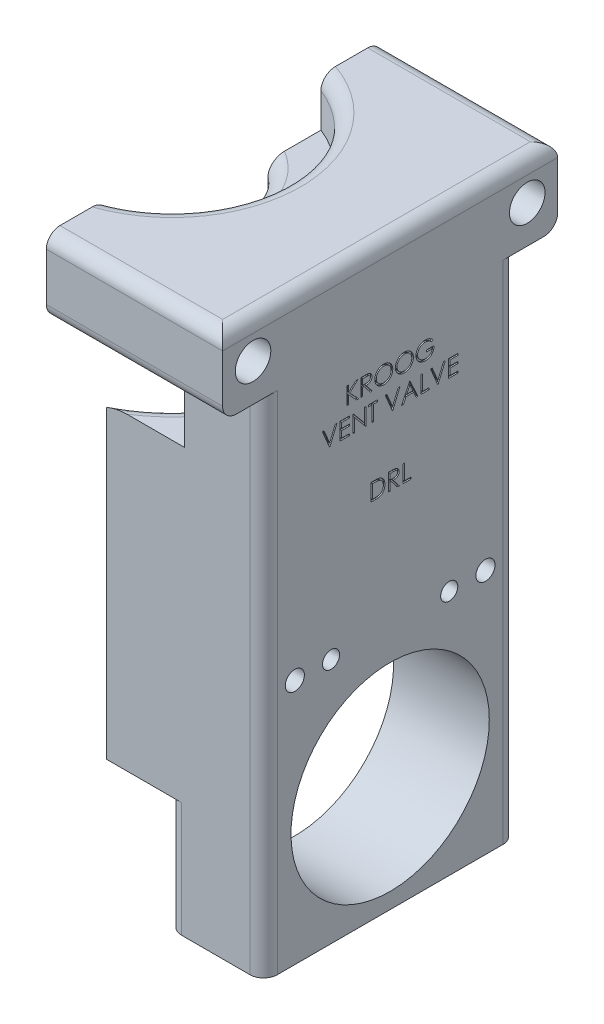
SolidWorks part; units mm, degrees
material "ABS"
ref_plane "Front Plane" through (0, 0, 0) normal (0, 0, 1) x (1, 0, 0)
ref_plane "Top Plane" through (0, 0, 0) normal (0, 1, 0) x (1, 0, 0)
ref_plane "Right Plane" through (0, 0, 0) normal (1, 0, 0) x (0, 0, -1)
sketch "Sketch2" plane through (0, 0, 0) normal (1, 0, 0) x (0, 0, -1)
  line L7 (-23.495, -21.336) -> (23.495, -21.336)
  line L8 (-23.495, -21.336) -> (-23.495, 72.644)
  line L9 (-23.495, 86.614) -> (23.495, 86.614)
  line L10 (23.495, -21.336) -> (23.495, 72.644)
  line L11 (-23.495, 86.614) -> (-31.115, 86.614)
  line L13 (-23.495, 72.644) -> (-31.115, 72.644)
  line L14 (-31.115, 86.614) -> (-31.115, 72.644)
  line L15 (23.495, 86.614) -> (31.115, 86.614)
  line L17 (23.495, 72.644) -> (31.115, 72.644)
  line L18 (31.115, 86.614) -> (31.115, 72.644)
  circle A0 centre (0, 0) radius 18.415
  point P13 (0, -21.336)
  dimension "D1" = 36.83
  dimension "D2" = 21.336
  dimension "D3" = 46.99
  dimension "D4" = 107.95
  dimension "D5" = 13.97
  dimension "D6" = 7.62
extrude "Boss-Extrude1" add sketch "Sketch2" along normal blind 17.78
sketch "Sketch4" plane through (0, 0, 0) normal (-1, 0, 0) x (0, 0, 1)
  line L0 (-23.495, -21.336) -> (-23.495, 72.644) construction
  line L1 (-23.495, 18.796) -> (23.495, 18.796)
  line L2 (-23.495, 18.796) -> (-23.495, 72.644)
  line L4 (23.495, 18.796) -> (23.495, 72.644)
  line L5 (31.115, 86.614) -> (31.115, 72.644) construction
  line L6 (31.115, 72.644) -> (23.495, 72.644) construction
  line L7 (-23.495, 72.644) -> (-31.115, 72.644) construction
  line L8 (-31.115, 72.644) -> (-31.115, 86.614) construction
  line L9 (-31.115, 86.614) -> (31.115, 86.614) construction
  line L10 (31.115, 86.614) -> (31.115, 72.644)
  line L11 (31.115, 72.644) -> (23.495, 72.644)
  line L12 (-23.495, 72.644) -> (-31.115, 72.644)
  line L13 (-31.115, 72.644) -> (-31.115, 86.614)
  line L14 (-31.115, 86.614) -> (31.115, 86.614)
  line L15 (23.495, 72.644) -> (23.495, -21.336) construction
  dimension "D1" = 18.796
extrude "Boss-Extrude2" add sketch "Sketch4" along normal blind 11.43
sketch "Sketch5" plane through (0, 86.614, 0) normal (0, 1, 0) x (1, 0, 0)
  line L0 (0, 0) -> (-22.7305, 0) construction
  line L2 (-11.43, -31.115) -> (-11.43, 31.115) construction
  circle A0 centre (-22.7305, 0) radius 34.925
  circle A1 centre (-22.7305, 0) radius 25.4
  dimension "D2" = 69.85
  dimension "D3" = 50.8
  dimension "D1" = 11.3005
extrude "Cut-Extrude1" cut sketch "Sketch5" against normal blind 15.24 from offset 13.97 contours A1 A0 | A1 region at (-56.6676, 86.614, 0) region at (-22.7305, 86.614, 0) offset against normal yes
extrude "Cut-Extrude2" cut sketch "Sketch5<3>" against normal blind 41.91 from surface contours A1 region at (-22.7305, 86.614, 0) starting at face at (-1.8888, 57.404, 0)
sketch "Sketch5<3>" plane through (0, 86.614, 0) normal (0, 1, 0) x (1, 0, 0) same geometry as "Sketch5"
sketch "Sketch6" plane through (-11.43, 0, 0) normal (-1, 0, 0) x (0, 0, 1)
  line L4 (-31.115, 86.614) -> (-31.115, 72.644)
  line L5 (-31.115, 72.644) -> (31.115, 72.644)
  line L6 (-31.115, 86.614) -> (-31.115, 72.644)
  line L7 (31.115, 72.644) -> (31.115, 86.614)
  line L9 (-31.115, 72.644) -> (31.115, 72.644)
  line L12 (31.115, 72.644) -> (31.115, 86.614)
  line L13 (31.115, 86.614) -> (-31.115, 86.614)
  line L14 (31.115, 86.614) -> (-31.115, 86.614)
  dimension "D1" = 0
extrude "Boss-Extrude3" add sketch "Sketch6" along normal blind 3.5301
sketch "Sketch12" plane through (0, 0, 0) normal (-1, 0, 0) x (0, 0, 1)
  line L0 (-23.495, 18.796) -> (-11.3352, 18.796) construction
  line L1 (-23.495, 18.796) -> (-11.3352, 18.796)
  line L2 (-19.05, 0) -> (-23.495, 0)
  line L3 (-23.495, -21.336) -> (-23.495, 18.796) construction
  line L4 (-23.495, 0) -> (-23.495, 18.796)
  line L5 (19.05, 0) -> (23.495, 0)
  line L6 (11.3352, 18.796) -> (23.495, 18.796)
  line L7 (23.495, 0) -> (23.495, 18.796)
  line L8 (23.495, 18.796) -> (23.495, -21.336) construction
  line L9 (-11.3352, 18.796) -> (-11.3352, 15.3107)
  line L10 (-11.3352, 15.494) -> (-11.3352, 18.796) construction
  line L11 (11.3352, 18.796) -> (11.3352, 15.3107)
  line L12 (11.3352, 18.796) -> (11.3352, 15.494) construction
  arc A0 (-19.05, 0) -> (-11.3352, 15.3107) centre (0, 0) cw
  arc A1 (11.3352, 15.3107) -> (19.05, 0) centre (0, 0) cw
  dimension "D1" = 19.05
extrude "Boss-Extrude5" add sketch "Sketch12" along normal up to surface (11.43 mm away) up to face at (-11.43, 38.1, 23.1214)
sketch "Sketch13" plane through (17.78, 0, 0) normal (1, 0, 0) x (0, 0, -1)
  line L0 (-23.495, -21.336) -> (23.495, -21.336) construction
  line L1 (-23.495, 72.644) -> (-23.495, -21.336) construction
  line L2 (0, 0) -> (0, 86.614) construction
  line L4 (31.115, 86.614) -> (-31.115, 86.614) construction
  circle A0 centre (-17.7038, 24.384) radius 1.778
  circle A1 centre (-10.9728, 24.384) radius 1.5875
  circle A2 centre (17.7038, 24.384) radius 1.778
  circle A3 centre (10.9728, 24.384) radius 1.5875
  dimension "D3" = 3.556
  dimension "D5" = 3.175
  dimension "D1" = 45.72
  dimension "D2" = 5.7912
  dimension "D4" = 6.731
extrude "Cut-Extrude5" cut sketch "Sketch13" against normal through all
sketch "Sketch14" plane through (-11.43, 0, 0) normal (-1, 0, 0) x (0, 0, 1)
  line L0 (10.9728, 24.384) -> (17.7038, 24.384) construction
  line L1 (10.9728, 27.432) -> (17.7038, 27.432)
  line L2 (10.9728, 21.336) -> (17.7038, 21.336)
  line L3 (0, 0) -> (0, 57.404) construction
  line L5 (22.7477, 57.404) -> (-22.7477, 57.404) construction
  line L6 (-10.9728, 24.384) -> (-17.7038, 24.384) construction
  line L7 (-10.9728, 27.432) -> (-17.7038, 27.432)
  line L8 (-10.9728, 21.336) -> (-17.7038, 21.336)
  line L9 (-7.9248, 24.384) -> (-7.9248, 21.336)
  line L10 (-20.7518, 49.784) -> (-7.9248, 49.784)
  line L11 (-20.7518, 49.784) -> (-20.7518, 24.384)
  line L12 (-20.7518, 24.384) -> (-7.9248, 24.384)
  line L13 (-7.9248, 49.784) -> (-7.9248, 24.384)
  line L14 (-20.7518, 49.784) -> (-7.9248, 24.384) construction
  line L15 (-20.7518, 24.384) -> (-7.9248, 49.784) construction
  line L16 (20.7518, 49.784) -> (7.9248, 49.784)
  line L17 (20.7518, 49.784) -> (20.7518, 24.384)
  line L18 (20.7518, 24.384) -> (7.9248, 24.384)
  line L19 (7.9248, 49.784) -> (7.9248, 24.384)
  line L20 (20.7518, 49.784) -> (7.9248, 24.384) construction
  line L21 (20.7518, 24.384) -> (7.9248, 49.784) construction
  line L22 (-10.9728, 21.336) -> (-7.9248, 21.336)
  line L23 (7.9248, 24.384) -> (7.9248, 21.336)
  line L24 (10.9728, 21.336) -> (7.9248, 21.336)
  arc A0 (10.9728, 27.432) -> (10.9728, 21.336) centre (10.9728, 24.384) ccw
  arc A1 (17.7038, 21.336) -> (17.7038, 27.432) centre (17.7038, 24.384) ccw
  arc A2 (-10.9728, 27.432) -> (-10.9728, 21.336) centre (-10.9728, 24.384) cw
  arc A3 (-17.7038, 21.336) -> (-17.7038, 27.432) centre (-17.7038, 24.384) cw
  point P4 (14.3383, 24.384)
  point P17 (-14.3383, 24.384)
  point P22 (-14.3383, 37.084)
  point P27 (14.3383, 37.084)
  line M47 (-11.3352, 18.796) -> (-22.7477, 18.796)
  dimension "D1" = 3.048
  dimension "D2" = 25.4
extrude "Cut-Extrude6" cut sketch "Sketch14" against normal blind 13.97 contours A3 L8 A2 L12 M47 | L9 A2 L22 | L11 A3 L7 A2 L13 L10 | A3 L12 A2 L7 | L2 A1 L18 A0 | A0 L23 L24 | L18 A1 L1 A0 | A1 L17 L16 L19 A0 L1 region at (-11.43, 38.4454, 14.3383) region at (-11.43, 25.8122, 14.3383) region at (-11.43, 22.0168, 8.6056) region at (-11.43, 22.9558, 14.3383) region at (-11.43, 25.8122, -14.3383) region at (-11.43, 38.4454, -14.3383) region at (-11.43, 22.9558, -14.3383) region at (-11.43, 22.0168, -8.6056)
sketch "Sketch15" plane through (-14.9601, 0, 0) normal (-1, 0, 0) x (0, 0, 1)
  line L0 (-31.115, 79.629) -> (-19.812, 79.629) construction
  line L1 (-31.115, 86.614) -> (-31.115, 72.644) construction
  line L3 (0, 72.644) -> (0, 86.614) construction
  line L4 (-31.115, 72.644) -> (31.115, 72.644) construction
  line L5 (31.115, 86.614) -> (-31.115, 86.614) construction
  line L6 (0, 0) -> (0, 86.614) construction
  circle A0 centre (-25.4635, 79.629) radius 3.302
  circle A1 centre (25.4635, 79.629) radius 3.302
  dimension "D1" = 6.604
  dimension "D2" = 19.812
extrude "Cut-Extrude7" cut sketch "Sketch15" against normal through all
sketch "Sketch17" plane through (0, 86.614, 0) normal (0, 1, 0) x (1, 0, 0)
  line L0 (-14.9601, -31.115) -> (-14.9601, 31.115) construction
  circle A0 centre (-22.7071, 0) radius 21.336
  dimension "D2" = 42.672
  dimension "D1" = 7.747
extrude "Cut-Extrude9" cut sketch "Sketch17" against normal blind 8.89
sketch "Sketch18" plane through (0, 77.724, 0) normal (0, 1, 0) x (1, 0, 0)
  line L0 (-22.7071, 0) -> (0, 0) construction
  arc A0 (-14.9601, -19.8799) -> (-14.9601, 19.8799) centre (-22.7071, 0) ccw construction
  arc A1 (-14.9601, -19.8799) -> (-14.9601, 19.8799) centre (-22.7071, 0) ccw construction
  circle A2 centre (-22.7071, 0) radius 12.7
  circle A3 centre (-5.2299, 0) radius 2.0509
  dimension "D1" = 25.4
  dimension "D2" = 4.1017
  dimension "D3" = 17.4772
extrude "Cut-Extrude10" cut sketch "Sketch18" against normal blind 8.89
sketch "Sketch16" plane through (17.78, 0, 0) normal (1, 0, 0) x (0, 0, -1)
  line L0 (-23.495, 63.754) -> (23.495, 63.754) construction
  line L1 (-23.495, 58.674) -> (23.495, 58.674) construction
  line L2 (23.495, -21.336) -> (23.495, 72.644) construction
  line L3 (-23.495, 72.644) -> (-23.495, -21.336) construction
  line L4 (-23.495, 45.974) -> (23.495, 45.974) construction
  line L5 (31.115, 86.614) -> (-31.115, 86.614) construction
  text T0 "KROOG\r\n"
  text T1 "VENT VALVE"
  text T2 "DRL"
  dimension "D1" = 22.86
  dimension "D2" = 12.7
  dimension "D3" = 5.08
extrude "Cut-Extrude8" cut sketch "Sketch16" against normal blind 0.254
fillet "Fillet1" radius 2.54 2 edges at (-1.3711, 86.614, 0) (-10.0071, 77.724, 0)
fillet "Fillet6" radius 1.27 4 edges at (2.54, 24.384, -15.9258) (2.54, 24.384, -9.3853) (2.54, 24.384, 19.4818) (2.54, 24.384, 12.5603)
fillet "Fillet7" radius 2.54 10 edges at (2.6695, 57.404, 0) (0, -10.668, -23.495) (0, -10.668, 23.495) (17.78, 25.654, -23.495) (17.78, 25.654, 23.495) (17.78, 86.614, 0) (1.41, 72.644, 31.115) (1.41, 86.614, 31.115) (1.41, 72.644, -31.115) (1.41, 86.614, -31.115)
sketch "Sketch19" plane through (0, 72.644, 0) normal (0, -1, 0) x (1, 0, 0)
  circle A0 centre (-5.2299, 0) radius 4.064
  dimension "D1" = 8.128
extrude "Cut-Extrude11" cut sketch "Sketch19" against normal blind 1.27
